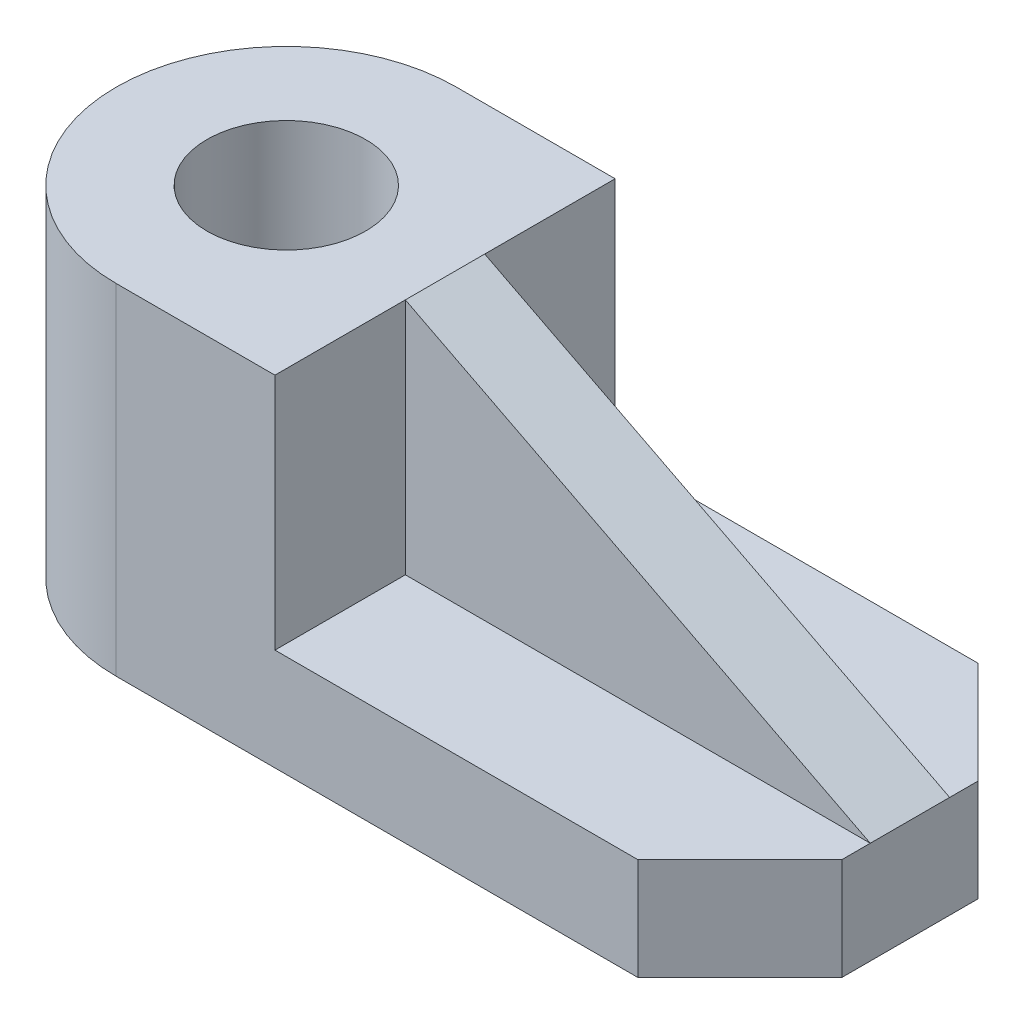
SolidWorks part; units mm, degrees
ref_plane "정면" through (0, 0, 0) normal (0, 0, 1) x (1, 0, 0)
ref_plane "윗면" through (0, 0, 0) normal (0, 1, 0) x (1, 0, 0)
ref_plane "우측면" through (0, 0, 0) normal (1, 0, 0) x (0, 0, -1)
sketch "스케치1" plane through (0, 0, 0) normal (0, 0, 1) x (1, 0, 0)
  line L0 (0, 0) -> (-70, 0)
  line L1 (-70, 0) -> (-70, 30)
  line L2 (-70, 30) -> (-41, 30)
  line L3 (-41, 30) -> (-41, 9)
  line L4 (-41, 9) -> (0, 9)
  line L5 (0, 9) -> (0, 0)
  dimension "D1" = 29
  dimension "D2" = 30
  dimension "D3" = 70
  dimension "D4" = 9
extrude "보스-돌출1" add sketch "스케치1" along normal blind 30
fillet "필렛1" radius 15 2 edges at (-70, 15, 0) (-70, 15, 30)
sketch "스케치2" plane through (0, 30, 0) normal (0, 1, 0) x (1, 0, 0)
  circle A0 centre (-55, -15) radius 7
  arc A1 (-55, 0) -> (-70, -15) centre (-55, -15) ccw construction
  dimension "D1" = 14
extrude "컷-돌출1" cut sketch "스케치2" against normal through all
sketch "스케치3" plane through (0, 0, 30) normal (0, 0, 1) x (1, 0, 0)
  line L0 (-41, 30) -> (0, 9)
  line L7 (-41, 30) -> (-55, 30)
  line L8 (-55, 30) -> (-55, 0)
  line L9 (-55, 0) -> (0, 0)
  line L10 (0, 0) -> (0, 9)
  line L11 (0, 9) -> (-41, 9)
  line L12 (-41, 9) -> (-41, 30)
  line L13 (-41, 30) -> (-55, 30)
  line L14 (-55, 30) -> (-55, 0)
  line L15 (-55, 0) -> (0, 0)
  line L16 (0, 0) -> (0, 9)
  line M5 (0, 9) -> (-41, 9)
  line M6 (-41, 9) -> (-41, 30)
  dimension "D1" = 0
extrude "보스-돌출3" add sketch "스케치3" against normal blind 7 from offset 11.5 contours L0 M6 M5 region at (-27.3333, 16, 30) offset against normal yes
chamfer "모따기1" distance 9 2 edges at (0, 4.5, 0) (0, 4.5, 30)
